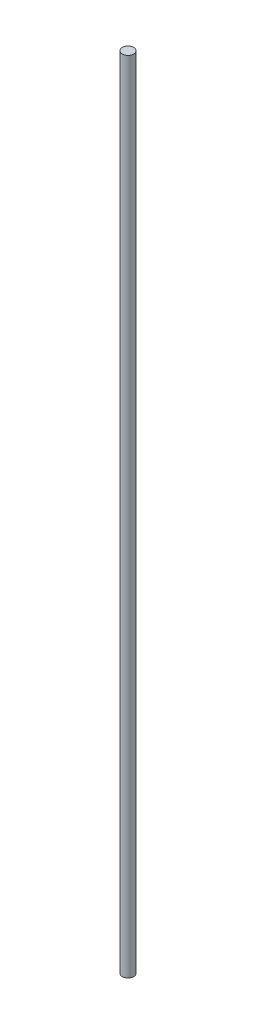
SolidWorks part; units mm, degrees
ref_plane "Front Plane" through (0, 0, 0) normal (0, 0, 1) x (1, 0, 0)
ref_plane "Top Plane" through (0, 0, 0) normal (0, 1, 0) x (1, 0, 0)
ref_plane "Right Plane" through (0, 0, 0) normal (1, 0, 0) x (0, 0, -1)
sketch "Sketch1" plane through (0, 0, 0) normal (0, 1, 0) x (1, 0, 0)
  circle A0 centre (0, 0) radius 4
  dimension "D1" = 8
extrude "Boss-Extrude1" add sketch "Sketch1" along normal blind 555 contours A0
